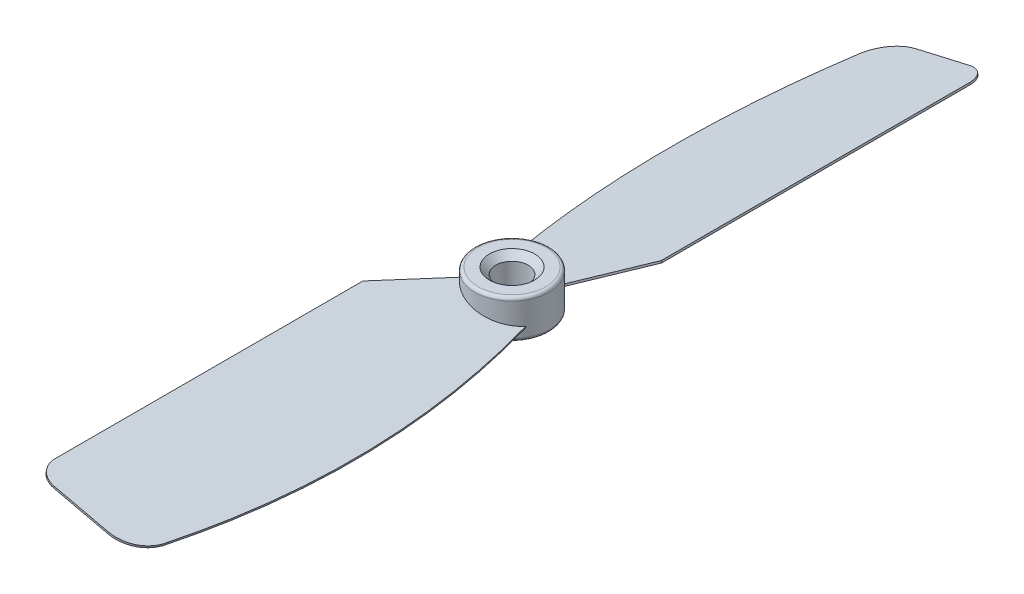
SolidWorks part; units mm, degrees
ref_plane "Front Plane" through (0, 0, 0) normal (0, 0, 1) x (1, 0, 0)
ref_plane "Top Plane" through (0, 0, 0) normal (0, 1, 0) x (1, 0, 0)
ref_plane "Right Plane" through (0, 0, 0) normal (1, 0, 0) x (0, 0, -1)
sketch "Sketch1" plane through (0, 0, 0) normal (0, 1, 0) x (1, 0, 0)
  circle A0 centre (0, 0) radius 5.75
  dimension "D1" = 11.5
extrude "Boss-Extrude1" add sketch "Sketch1" along normal mid plane 6
sketch "Sketch2" plane through (0, 0, 0) normal (0, 0, 1) x (1, 0, 0)
  line L0 (-5.75, 1.3275) -> (5.75, -1.3275) construction
  line L1 (-5.75, 3) -> (-5.75, -3) construction
  line L2 (5.75, -3) -> (5.75, 3) construction
  line L3 (-5.75, -3) -> (5.75, -3) construction
  dimension "D1" = 13
ref_plane "Plane1" through (0, 0, 0) normal (-0.225, -0.9744, 0) x (0.9744, -0.225, 0)
sketch "Sketch3" plane through (0, 0, 0) normal (-0.225, -0.9744, 0) x (0.9744, -0.225, 0)
  line L0 (-4.1858, 2.8595) -> (-10.4569, 12.8861)
  line L1 (-10.4569, 12.8861) -> (-10.4569, 60.5)
  line L2 (-7.4569, 63.5) -> (1.169, 63.5)
  arc A0 (6.126, 59.1543) -> (1.169, 63.5) centre (1.169, 58.5) ccw
  arc A1 (-10.4569, 60.5) -> (-7.4569, 63.5) centre (-7.4569, 60.5) cw
  arc A2 (-4.1858, 2.8595) -> (5.0864, 2.8595) centre (0.4503, 0.1825) cw
  ellipse E0 centre (0.6749, 0) end of major axis (0.6749, 5.75) minor radius 5.6026 construction
  ellipse E1 centre (0.6749, 0) end of major axis (0.6749, 5.75) minor radius 5.6026 (5.3137, 3.2244) -> (5.2134, 3.3714) ccw
  spline S0 degree 2 poles (5.0864, 2.8595) (12.032, 30.6175) (6.126, 59.1543) knots 0 0 0 1 1 1
  dimension "D2" = 5
  dimension "D3" = 3
  dimension "D1" = 63.5
extrude "Boss-Extrude3" add sketch "Sketch3" along normal mid plane 0.3 contours A2 S0 A0 L2 A1 L1 L0 region at (-1.1857, 0.2737, 34.3523)
pattern_circular "CirPattern1" count 2 over 360 about axis through (0, 3, 0) along (0, -1, 0) of "Boss-Extrude3" reverse direction yes
sketch "Sketch5" plane through (0, 3, 0) normal (0, 1, 0) x (1, 0, 0)
  circle A0 centre (0, 0) radius 2.5
  dimension "D1" = 5
extrude "Cut-Extrude1" cut sketch "Sketch5" against normal through all
fillet "Fillet1" radius 0.5 2 edges at (0, -3, 5.75) (0, 3, 5.75)
fillet "Fillet2" radius 1 2 edges at (0, -3, 2.5) (0, 3, 2.5) profile chamfer
